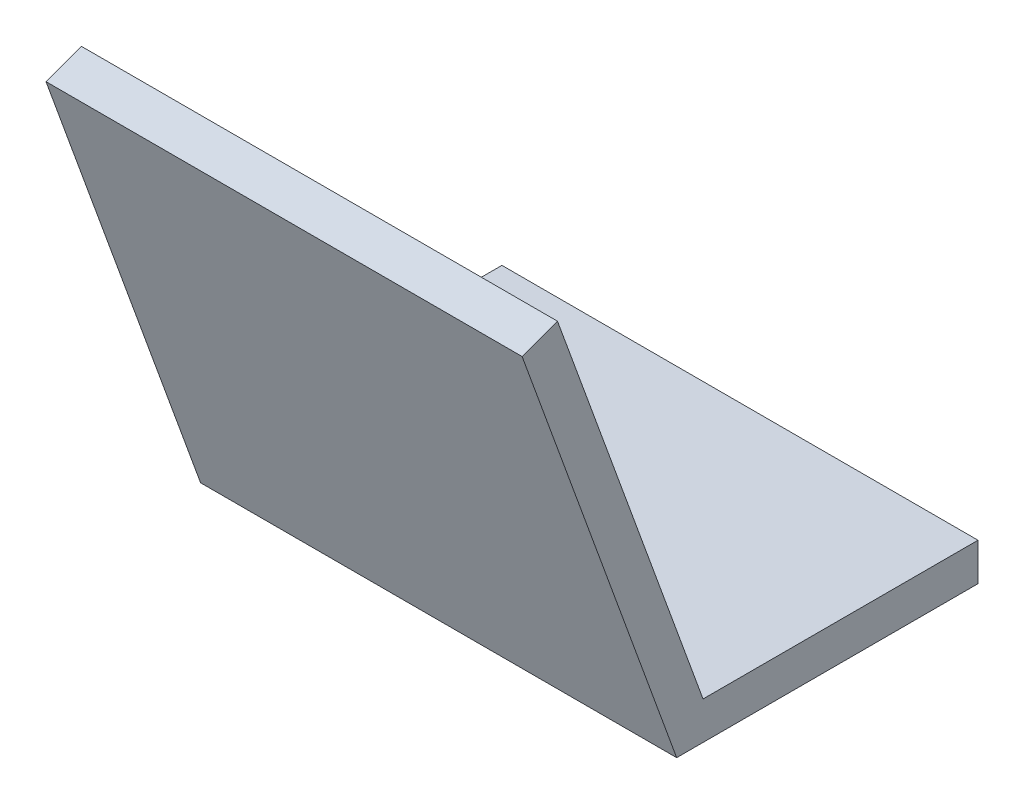
SolidWorks part; units mm, degrees
ref_plane "Front Plane" through (0, 0, 0) normal (0, 0, 1) x (1, 0, 0)
ref_plane "Top Plane" through (0, 0, 0) normal (0, 1, 0) x (1, 0, 0)
ref_plane "Right Plane" through (0, 0, 0) normal (1, 0, 0) x (0, 0, -1)
sketch "Sketch2" plane through (0, 0, 0) normal (0, 1, 0) x (1, 0, 0)
  line L1 (-58.4378, 24.3204) -> (-18.3058, 24.3204)
  line L2 (-58.4378, 24.3204) -> (-58.4378, -1.0796)
  line L3 (-58.4378, -1.0796) -> (-18.3058, -1.0796)
  line L4 (-18.3058, 24.3204) -> (-18.3058, -1.0796)
  dimension "D1" = 40.132
  dimension "D2" = 25.4
extrude "Boss-Extrude1" add sketch "Sketch2" along normal blind 3.175
sketch "Sketch3" plane through (-18.3058, 0, 0) normal (1, 0, 0) x (0, 0, -1)
  line L0 (-1.0796, 0) -> (-14.1105, 35.8023)
  line L1 (-14.1105, 35.8023) -> (-11.127, 36.8882)
  line L2 (-11.127, 36.8882) -> (1.1436, 3.175)
  line L3 (-1.0796, 3.175) -> (24.3204, 3.175) construction
  line L4 (-1.0796, 3.175) -> (-1.0796, 0) construction
  line L6 (-1.0796, 0) -> (1.1436, 3.175)
  dimension "D1" = 3.175
  dimension "D2" = 20
  dimension "D3" = 38.1
extrude "Boss-Extrude2" add sketch "Sketch3" against normal blind 40.132
sketch "Sketch5" plane through (0, -0.347, 0.9533) normal (0, -0.342, 0.9397) x (1, 0, 0)
  line L0 (-58.4378, 38.4692) -> (-18.3058, 38.4692) construction
  line L1 (-44.7218, 38.4692) -> (-32.0218, 38.4692)
  line L2 (-44.7218, 38.4692) -> (-44.7218, 35.2942)
  line L3 (-44.7218, 35.2942) -> (-32.0218, 35.2942)
  line L4 (-32.0218, 38.4692) -> (-32.0218, 35.2942)
  point P4 (-38.3718, 38.4692)
  dimension "D1" = 3.175
  dimension "D2" = 12.7
